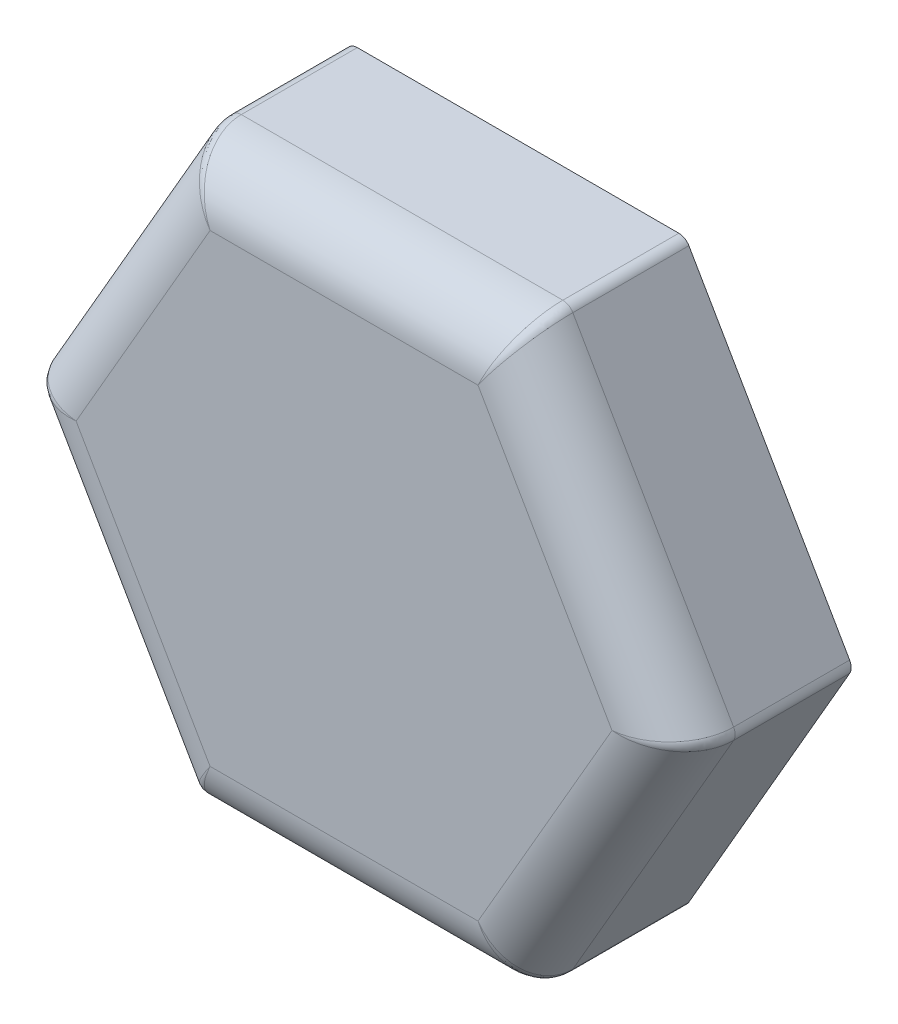
SolidWorks part; units mm, degrees
material "Dostosowane tworzywo sztuczne"
ref_plane "Płaszczyzna przednia" through (0, 0, 0) normal (0, 0, 1) x (1, 0, 0)
ref_plane "Płaszczyzna górna" through (0, 0, 0) normal (0, 1, 0) x (1, 0, 0)
ref_plane "Płaszczyzna prawa" through (0, 0, 0) normal (1, 0, 0) x (0, 0, -1)
sketch "Szkic1" plane through (0, 0, 0) normal (0, 0, 1) x (1, 0, 0)
  line L1 (14.4338, -25) -> (28.8675, 0)
  line L2 (28.8675, 0) -> (14.4338, 25)
  line L3 (14.4338, 25) -> (-14.4338, 25)
  line L4 (-14.4338, 25) -> (-28.8675, 0)
  line L5 (-28.8675, 0) -> (-14.4338, -25)
  line L6 (-14.4338, -25) -> (14.4338, -25)
  circle A0 centre (0, 0) radius 25 construction
  point P1 (28.8396, 1.2698)
  point P10 (0, 0)
  point P11 (28.8434, -1.1786)
  dimension "D1" = 50
extrude "Dodanie-wyciągnięcie1" add sketch "Szkic1" along normal blind 15
fillet "Zaokrąglenie1" radius 5 6 edges at (0, 25, 15) (-21.6506, 12.5, 15) (-21.6506, -12.5, 15) (0, -25, 15) (21.6506, -12.5, 15) (21.6506, 12.5, 15)
fillet "Zaokrąglenie2" radius 1 12 edges at (-13.5882, 23.5355, 13.5355) (-27.1765, 0, 13.5355) (-13.5882, -23.5355, 13.5355) (13.5882, -23.5355, 13.5355) (27.1765, 0, 13.5355) (13.5882, 23.5355, 13.5355) (-14.4338, 25, 5) (-28.8675, 0, 5) (-14.4338, -25, 5) (14.4338, -25, 5) (28.8675, 0, 5) (14.4338, 25, 5)
sketch "Szkic3" plane through (0, 0, 0) normal (0, 0, -1) x (-1, 0, 0)
  line L0 (13.8564, -25) -> (-13.8564, -25) construction
  line L1 (4.9075, -8.5) -> (9.815, 0)
  line L2 (9.815, 0) -> (4.9075, 8.5)
  line L3 (4.9075, 8.5) -> (-4.9075, 8.5)
  line L4 (-4.9075, 8.5) -> (-9.815, 0)
  line L5 (-9.815, 0) -> (-4.9075, -8.5)
  line L6 (-4.9075, -8.5) -> (4.9075, -8.5)
  circle A0 centre (0, 0) radius 11.5
  circle A1 centre (0, 0) radius 8.5 construction
  dimension "D2" = 3
  dimension "D1" = 17
extrude "Dodanie-wyciągnięcie2" add sketch "Szkic3" along normal blind 6
